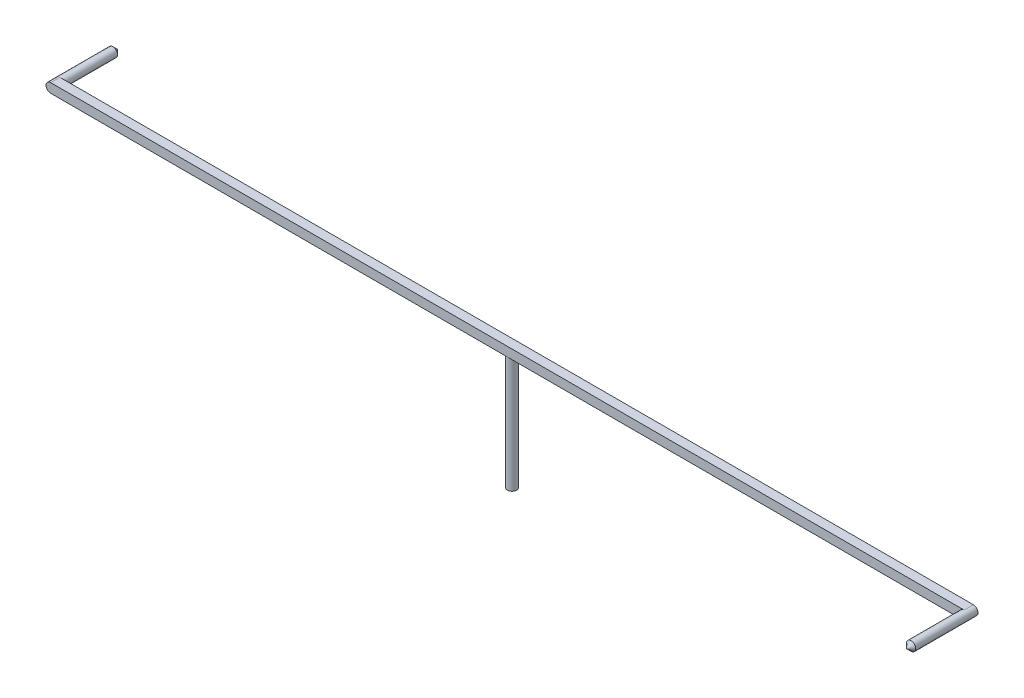
SolidWorks part; units mm, degrees
ref_plane "前视基准面" through (0, 0, 0) normal (0, 0, 1) x (1, 0, 0)
ref_plane "上视基准面" through (0, 0, 0) normal (0, 1, 0) x (1, 0, 0)
ref_plane "右视基准面" through (0, 0, 0) normal (1, 0, 0) x (0, 0, -1)
sketch "草图1" plane through (0, 0, 0) normal (0, 1, 0) x (1, 0, 0)
  circle A0 centre (0, 0) radius 0.4
  dimension "D1" = 0.8
extrude "凸台-拉伸1" add sketch "草图1" along normal blind 10
sketch "草图2" plane through (0, 10, 0) normal (0, 1, 0) x (1, 0, 0)
  line L1 (-40, 0.4) -> (40, 0.4)
  line L2 (-40, 0.4) -> (-40, -0.4)
  line L3 (-40, -0.4) -> (40, -0.4)
  line L4 (40, 0.4) -> (40, -0.4)
  circle A0 centre (0, 0) radius 0.4 construction
  dimension "D1" = 40
  dimension "D2" = 40
extrude "凸台-拉伸2" add sketch "草图2" along normal blind 0.8
fillet "圆角1" radius 0.4 4 edges at (40, 10, 0) (40, 10.8, 0) (-40, 10, 0) (-40, 10.8, 0)
sketch "草图3" plane through (0, 0, 0.4) normal (0, 0, 1) x (1, 0, 0)
  circle A0 centre (39.6, 10.4) radius 0.4
  dimension "D1" = 0.8
extrude "凸台-拉伸3" add sketch "草图3" along normal blind 5
sketch "草图4" plane through (0, 0, -0.4) normal (0, 0, -1) x (-1, 0, 0)
  circle A0 centre (39.6, 10.4) radius 0.4
  dimension "D1" = 0.8
extrude "凸台-拉伸4" add sketch "草图4" along normal blind 5
chamfer "倒角1" distance 0.4 angle 45 2 edges at (-40, 10.4, -5.4) (40, 10.4, 5.4)
